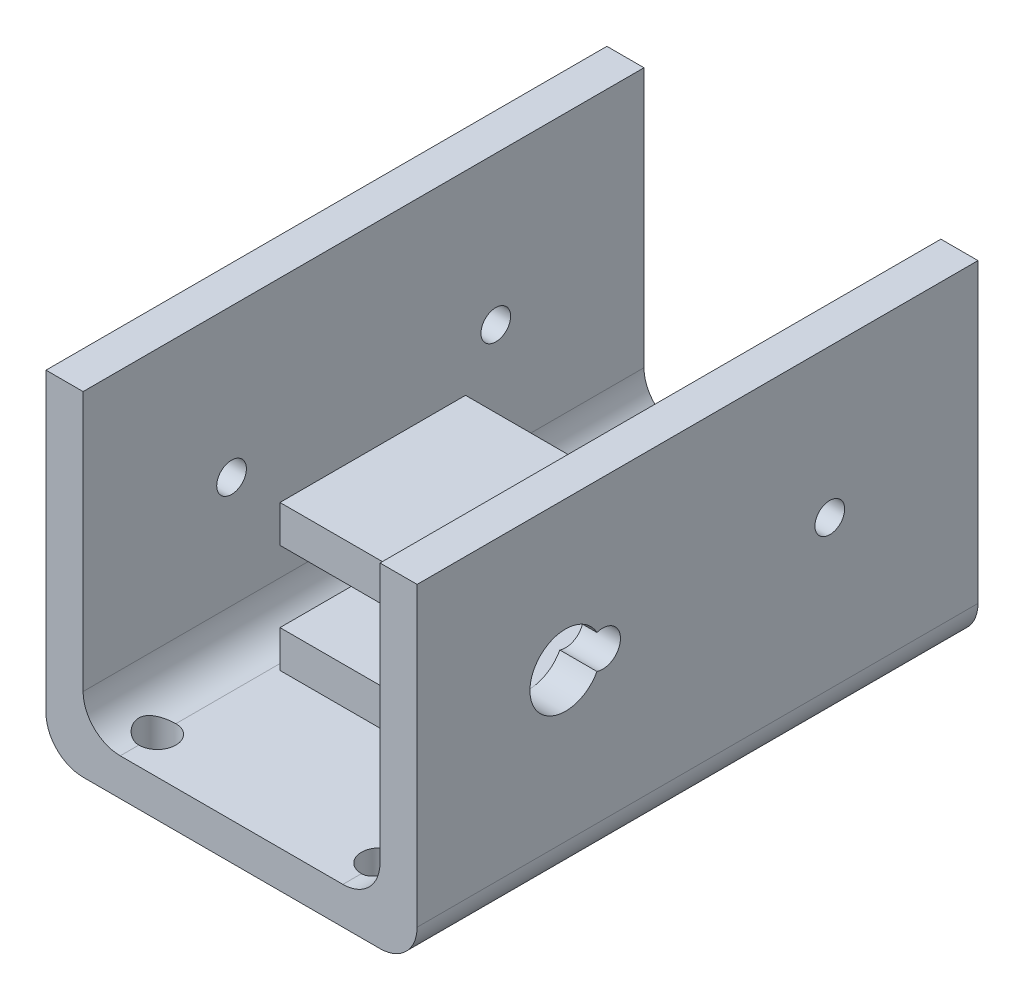
SolidWorks part; units mm, degrees
ref_plane "Front Plane" through (0, 0, 0) normal (0, 0, 1) x (1, 0, 0)
ref_plane "Top Plane" through (0, 0, 0) normal (0, 1, 0) x (1, 0, 0)
ref_plane "Right Plane" through (0, 0, 0) normal (1, 0, 0) x (0, 0, -1)
sketch "Sketch1" plane through (0, 0, 0) normal (0, 1, 0) x (1, 0, 0)
  line L0 (-25.4, -48.006) -> (-25.4, 47.9667)
  line L1 (-31.75, 47.9667) -> (31.75, 47.9667)
  line L2 (-31.75, 47.9667) -> (-31.75, -48.006)
  line L3 (-31.75, -48.006) -> (31.75, -48.006)
  line L4 (31.75, 47.9667) -> (31.75, -48.006)
  line L5 (25.4, 47.9667) -> (25.4, -48.006)
  circle A2 centre (0, 0) radius 3.81
  circle A3 centre (-19.05, -41.656) radius 3.175
  circle A4 centre (19.05, -41.656) radius 3.175
  circle A5 centre (-19.05, 41.6167) radius 3.175
  circle A6 centre (19.05, 41.6167) radius 3.175
  point P19 (0, 0)
  point P20 (0, 0)
  point P21 (0, 0)
  point P22 (0, 0)
  dimension "D7" = 7.62
  dimension "D8" = 6.35
  dimension "D9" = 6.35
  dimension "D10" = 6.35
  dimension "D11" = 6.35
  dimension "D1" = 31.75
  dimension "D2" = 63.5
  dimension "D3" = 48.006
  dimension "D4" = 95.9727
  dimension "D5" = 6.35
  dimension "D6" = 6.35
  dimension "D12" = 6.35
  dimension "D13" = 6.35
  dimension "D14" = 6.35
  dimension "D15" = 6.35
extrude "Boss-Extrude1" add sketch "Sketch1" along normal blind 6.35 contours L5 L1 L0 L3 A3 A2 region at (-24.3141, 0, 0.0197)
extrude "Boss-Extrude2" add sketch "Sketch1<3>" along normal blind 57.15 contours L2 L3 L0 L1 | L1 L5 L3 L4 region at (-28.575, 0, 0.0197) region at (28.575, 0, 0.0197)
sketch "Sketch1<3>" plane through (0, 0, 0) normal (0, 1, 0) x (1, 0, 0) same geometry as "Sketch1"
fillet "Fillet1" radius 6.35 4 edges at (25.4, 6.35, 0.0197) (-25.4, 6.35, 0.0197) (-31.75, 0, 0.0197) (31.75, 0, 0.0197)
sketch "Sketch2" plane through (31.75, 0, 0) normal (1, 0, 0) x (0, 0, -1)
  line L0 (-48.006, 6.35) -> (47.9667, 6.35) construction
  line L1 (47.9667, 57.15) -> (-48.006, 57.15) construction
  line L3 (-48.006, 57.15) -> (-48.006, 6.35) construction
  circle A0 centre (-22.606, 31.75) radius 6.096
  circle A1 centre (22.606, 31.75) radius 2.54
  circle A2 centre (-22.606, 31.75) radius 2.54
  circle A3 centre (-16.256, 31.75) radius 3.048
  point P11 (0, 0)
  dimension "D1" = 12.192
  dimension "D2" = 5.08
  dimension "D7" = 5.08
  dimension "D8" = 6.096
  dimension "D3" = 25.4
  dimension "D4" = 45.212
  dimension "D5" = 25.4
  dimension "D6" = 25.4
  dimension "D9" = 6.35
  dimension "D10" = 25.4
extrude "Cut-Extrude1" cut sketch "Sketch2" against normal up to surface (6.35 mm away) contours A2 | A0 A2 | A0 A3 | A0 A3 region at (31.75, 31.75, 17.8119) region at (31.75, 31.75, 15.2368) region at (31.75, 31.75, 19.4714) region at (31.75, 31.75, 22.606) up to face at (25.4, 34.925, 0.0197)
extrude "Cut-Extrude2" cut sketch "Sketch2<4>" against normal up to surface (63.5 mm away) contours A2 | A1 up to face at (-31.75, 31.75, 0.0197)
sketch "Sketch2<4>" plane through (31.75, 0, 0) normal (1, 0, 0) x (0, 0, -1) same geometry as "Sketch2"
sketch "Sketch3" plane through (25.4, 0, 0) normal (-1, 0, 0) x (0, 0, 1)
  line L1 (34.6419, 19.304) -> (2.8919, 19.304)
  line L2 (34.6419, 19.304) -> (34.6419, 25.654)
  line L3 (34.6419, 25.654) -> (2.8919, 25.654)
  line L4 (2.8919, 19.304) -> (2.8919, 25.654)
  line L6 (34.6419, 37.846) -> (2.8919, 37.846)
  line L7 (34.6419, 37.846) -> (34.6419, 44.196)
  line L8 (34.6419, 44.196) -> (2.8919, 44.196)
  line L9 (2.8919, 37.846) -> (2.8919, 44.196)
  circle A0 centre (22.606, 31.75) radius 6.096 construction
  point P12 (-36.6058, 15.4)
  point P13 (-28.8341, 55.4)
  point P14 (113.2971, 15.4)
  point P16 (0, 0)
  point P17 (0, 0)
  point P18 (0, 0)
  point P19 (0, 0)
  point P20 (0, 0)
  point P21 (0, 0)
  point P22 (0, 0)
  point P23 (0, 0)
  point P24 (94.6333, 55.4)
  point P25 (106.3377, 55.4)
  dimension "D3" = 6.096
  dimension "D4" = 6.096
  dimension "D1" = 6.35
  dimension "D2" = 6.35
  dimension "D7" = 31.75
extrude "Boss-Extrude4" add sketch "Sketch3" along normal blind 30.48
